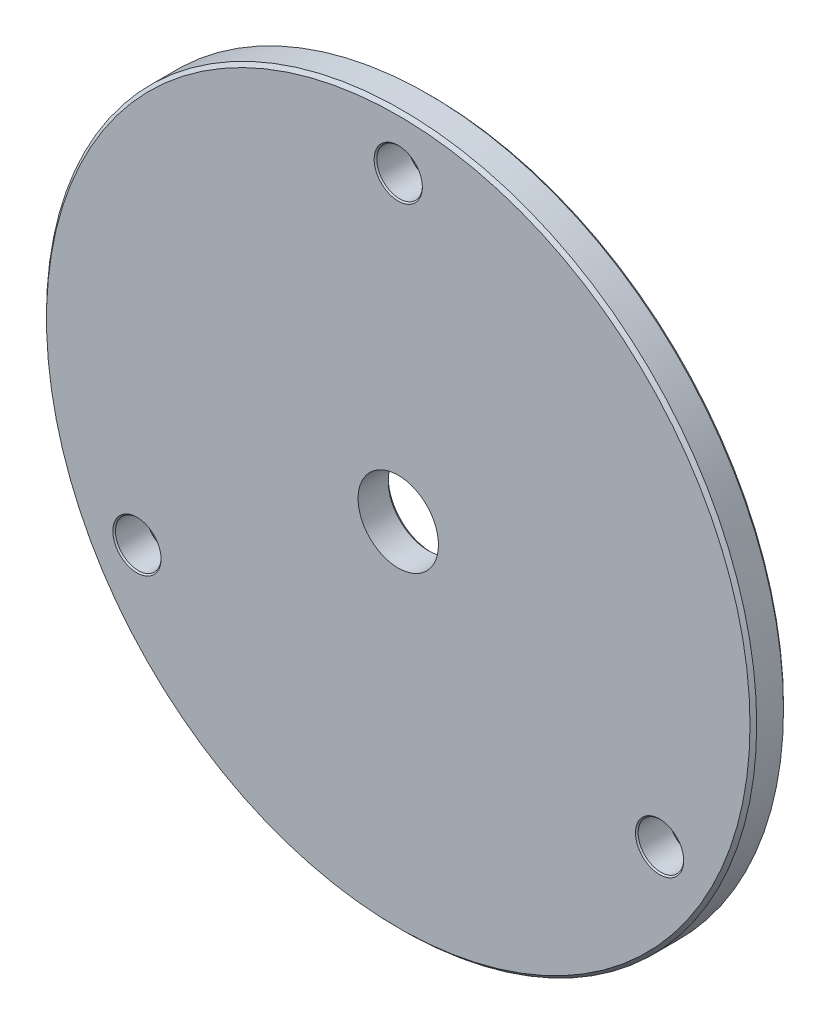
SolidWorks part; units mm, degrees
material "AISI 1020"
ref_plane "Plan de face" through (0, 0, 0) normal (0, 0, 1) x (1, 0, 0)
ref_plane "Plan de dessus" through (0, 0, 0) normal (0, 1, 0) x (1, 0, 0)
ref_plane "Plan de droite" through (0, 0, 0) normal (1, 0, 0) x (0, 0, -1)
sketch "Esquisse1" plane through (0, 0, 0) normal (0, 0, 1) x (1, 0, 0)
  circle A0 centre (0, 0) radius 53
  dimension "D1" = 106
extrude "Boss.-Extru.1" add sketch "Esquisse1" along normal blind 5
chamfer "Chanfrein1" distance 0.5 angle 45 2 edges at (53, 0, 0) (53, 0, 5)
hole_wizard "Trou pour taraudage pour trou taraudé M81" positions "Esquisse3" profile "Esquisse2" hole size "M8" standard "ISO" end condition through all
sketch "Esquisse3" plane through (0, 0, 5) normal (0, 0, 1) x (1, 0, 0)
  line L0 (0, 65.1988) -> (0, -70.7978) construction
  circle A0 centre (0, 0) radius 45.0333
  point P0 (0, 45.0333)
  point P11 (39, -22.5167)
  point P13 (-39, -22.5167)
  dimension "D1" = 78
  dimension "D2" = 78
  dimension "D3" = 78
sketch "Esquisse2" plane through (0, 45.0333, 5) normal (1, 0, 0) x (0, -1, 0)
  line L0 (0, 0) -> (0, 5)
  line L1 (0, 5) -> (3.4, 5)
  line L2 (3.4, 5) -> (3.4, 0)
  line L5 (3.4, 0) -> (0, 0)
  line L11 (0, -6.35) -> (0, 107.95) construction
  dimension "Diamètre du perçage jusqu'au prochain" = 6.8
  dimension "Profondeur du perçage jusqu'au prochain" = 5
ref_axis "Axe1" through (0, 0, 4.5) along (0, 0, -1)
chamfer "Chanfrein2" distance 0.2 angle 45 6 edges at (42.4, -22.5167, 5) (42.4, -22.5167, 0) (-35.6, -22.5167, 5) (-35.6, -22.5167, 0) (3.4, 45.0333, 5) (3.4, 45.0333, 0)
sketch "Esquisse4" plane through (0, 0, 5) normal (0, 0, 1) x (1, 0, 0)
  circle A0 centre (0, 0) radius 6
  dimension "D1" = 12
extrude "Enlèv. mat.-Extru.1" cut sketch "Esquisse4" against normal through all
chamfer "Chanfrein3" distance 0.5 angle 45 1 edges at (6, 0, 0)
